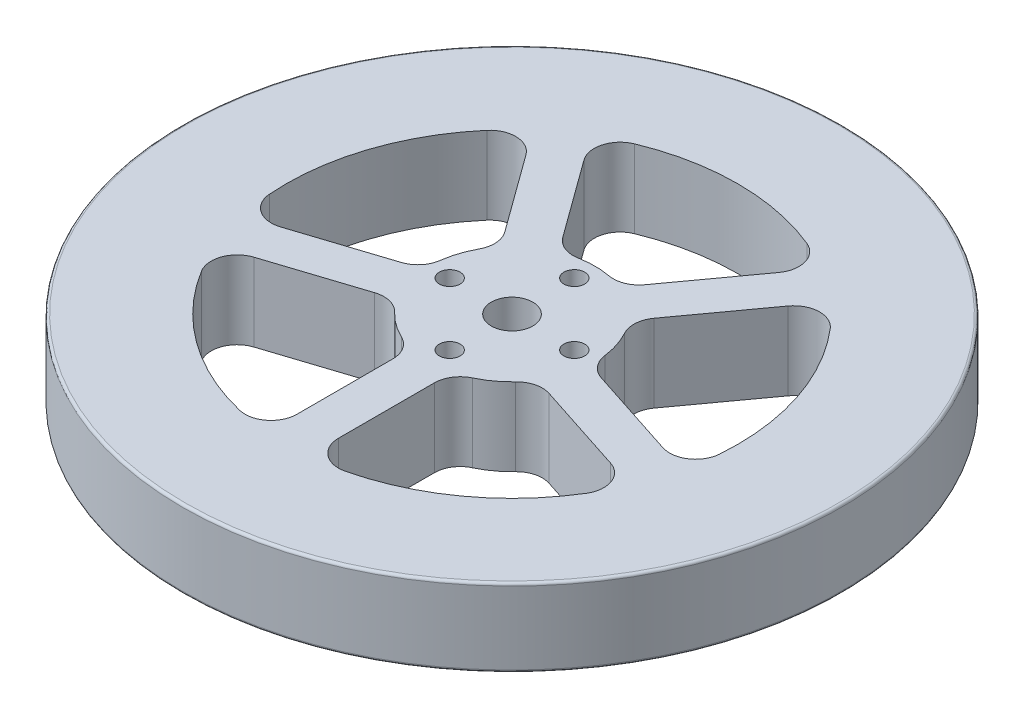
SolidWorks part; units mm, degrees
material "Polyethylene Cross-Linked"
ref_plane "Front Plane" through (0, 0, 0) normal (0, 0, 1) x (1, 0, 0)
ref_plane "Top Plane" through (0, 0, 0) normal (0, 1, 0) x (1, 0, 0)
ref_plane "Right Plane" through (0, 0, 0) normal (1, 0, 0) x (0, 0, -1)
sketch "Sketch2" plane through (0, 0, 0) normal (0, 1, 0) x (1, 0, 0)
  circle A0 centre (0, 0) radius 63.5
  point P13 (0, 0)
  point P19 (0, 0)
  dimension "D1" = 127
extrude "Boss-Extrude1" add sketch "Sketch2" along normal blind 15 contours A0 region at (0, 0, 0)
fillet "Fillet2" radius 0.5 2 edges at (0, 15, 63.5) (0, 0, 63.5)
sketch "Sketch5" plane through (0, 0, 0) normal (0, -1, 0) x (1, 0, 0)
  line L0 (0, 0) -> (0, 43.5)
  line L1 (-4, 15.4919) -> (-4, 43.3157)
  line L2 (4, 15.4919) -> (4, 43.3157)
  line L3 (-4, 29.4038) -> (4, 29.4038) construction
  line L4 (0, 0) -> (41.371, 13.4422)
  line L5 (13.4976, 8.5915) -> (39.9596, 17.1895)
  line L6 (15.9698, 0.983) -> (42.4317, 9.5811)
  line L7 (26.7286, 12.8905) -> (29.2008, 5.2821) construction
  line L8 (0, 0) -> (25.5687, -35.1922)
  line L9 (12.342, -10.1821) -> (28.6964, -32.692)
  line L10 (5.8699, -14.8844) -> (22.2243, -37.3943)
  line L11 (20.5192, -21.437) -> (14.0471, -26.1393) construction
  line L12 (0, 0) -> (-25.5687, -35.1922)
  line L13 (-5.8699, -14.8844) -> (-22.2243, -37.3943)
  line L14 (-12.342, -10.1821) -> (-28.6964, -32.692)
  line L15 (-14.0471, -26.1393) -> (-20.5192, -21.437) construction
  line L16 (0, 0) -> (-41.371, 13.4422)
  line L17 (-15.9698, 0.983) -> (-42.4317, 9.5811)
  line L18 (-13.4976, 8.5915) -> (-39.9596, 17.1895)
  line L19 (-29.2008, 5.2821) -> (-26.7286, 12.8905) construction
  arc A0 (-42.4317, 9.5811) -> (-28.6964, -32.692) centre (0, 0) ccw
  arc A1 (-15.9698, 0.983) -> (-12.342, -10.1821) centre (0, 0) ccw
  circle A2 centre (0, 0) radius 63.5 construction
  arc A3 (-22.2243, -37.3943) -> (22.2243, -37.3943) centre (0, 0) ccw
  arc A4 (28.6964, -32.692) -> (42.4317, 9.5811) centre (0, 0) ccw
  arc A5 (39.9596, 17.1895) -> (4, 43.3157) centre (0, 0) ccw
  arc A6 (-4, 43.3157) -> (-39.9596, 17.1895) centre (0, 0) ccw
  arc A7 (-4, 15.4919) -> (-13.4976, 8.5915) centre (0, 0) ccw
  arc A8 (13.4976, 8.5915) -> (4, 15.4919) centre (0, 0) ccw
  arc A9 (12.342, -10.1821) -> (15.9698, 0.983) centre (0, 0) ccw
  arc A10 (-5.8699, -14.8844) -> (5.8699, -14.8844) centre (0, 0) ccw
  point P43 (0, 0)
  dimension "D1" = 32
  dimension "D2" = 20
  dimension "D3" = 8
  dimension "D4" = 5
extrude "Cut-Extrude3" cut sketch "Sketch5" against normal up to next contours A7 L1 A6 L18 | A8 L5 A5 L2 | A9 L9 A4 L6 | A10 L13 A3 L10 | A1 L17 A0 L14 region at (-18.2727, 0, 25.1502) region at (18.2727, 0, 25.1502) region at (29.5658, 0, -9.6065) region at (0, 0, -31.0873) region at (-29.5658, 0, -9.6065)
sketch "Sketch6" plane through (0, 0, 0) normal (0, -1, 0) x (1, 0, 0)
  circle A0 centre (0, 0) radius 12 construction
  circle A1 centre (12, 0) radius 2
  circle A2 centre (0, -12) radius 2
  circle A3 centre (-12, 0) radius 2
  circle A4 centre (0, 12) radius 2
  circle A5 centre (0, 0) radius 4
  point P14 (0, 0)
  dimension "D1" = 24
  dimension "D2" = 4
  dimension "D4" = 8
  dimension "D3" = 4
extrude "Cut-Extrude4" cut sketch "Sketch6" against normal up to next contours A3 | A2 | A1 | A4
fillet "Fillet3" radius 5 20 edges at (13.4976, 7.5, 8.5915) (4, 7.5, 15.4919) (39.9596, 7.5, 17.1895) (4, 7.5, 43.3157) (-4, 7.5, 43.3157) (-4, 7.5, 15.4919) (-13.4976, 7.5, 8.5915) (-39.9596, 7.5, 17.1895) (-42.4317, 7.5, 9.5811) (-15.9698, 7.5, 0.983) (-12.342, 7.5, -10.1821) (-28.6964, 7.5, -32.692) (-22.2243, 7.5, -37.3943) (22.2243, 7.5, -37.3943) (5.8699, 7.5, -14.8844) (28.6964, 7.5, -32.692) (42.4317, 7.5, 9.5811) (-5.8699, 7.5, -14.8844) (12.342, 7.5, -10.1821) (15.9698, 7.5, 0.983)
extrude "Cut-Extrude5" cut sketch "Sketch6<4>" against normal through all
sketch "Sketch6<4>" plane through (0, 0, 0) normal (0, -1, 0) x (1, 0, 0) same geometry as "Sketch6"
